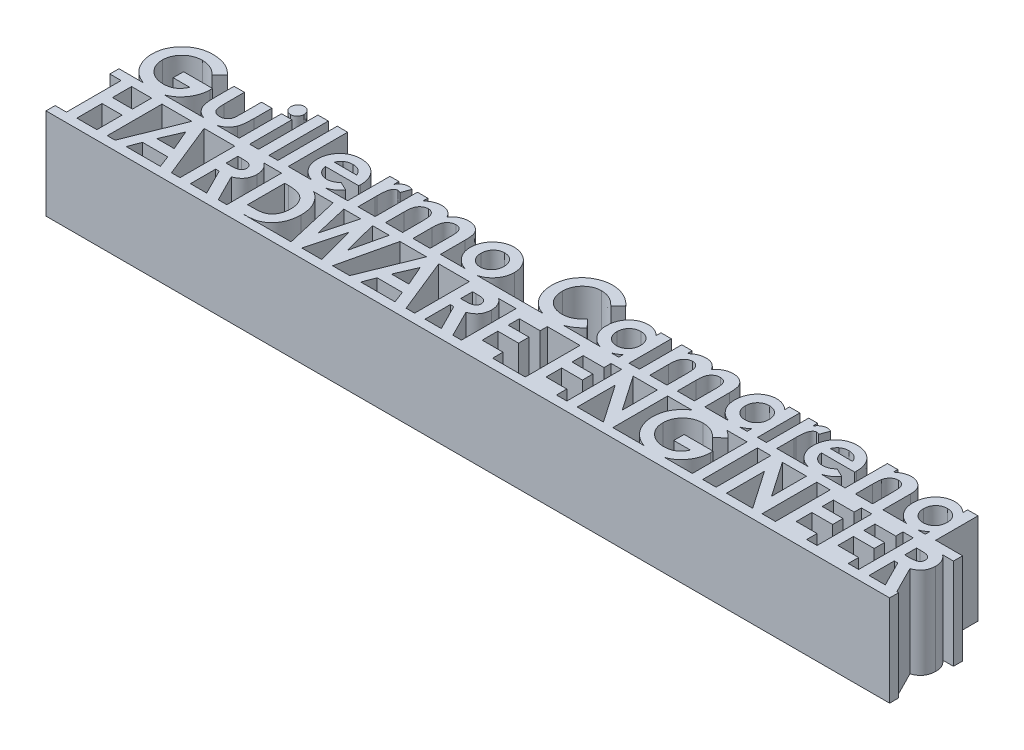
SolidWorks part; units mm, degrees
ref_plane "Front Plane" through (0, 0, 0) normal (0, 0, 1) x (1, 0, 0)
ref_plane "Top Plane" through (0, 0, 0) normal (0, 1, 0) x (1, 0, 0)
ref_plane "Right Plane" through (0, 0, 0) normal (1, 0, 0) x (0, 0, -1)
sketch "Sketch2" plane through (0, 0, 0) normal (0, 1, 0) x (1, 0, 0)
  text T0 "Guillermo Camarena" font "Century Gothic" height in points 48
extrude "Boss-Extrude1" add sketch "Sketch2" along normal blind 20
sketch "Sketch3" plane through (0, 0, 0) normal (0, 1, 0) x (1, 0, 0)
  line L1 (0, 0) -> (185, 0)
  line L2 (0, 0) -> (0, -2)
  line L3 (0, -2) -> (185, -2)
  line L4 (185, 0) -> (185, -2)
  dimension "D1" = 185
  dimension "D2" = 2
extrude "Boss-Extrude2" add sketch "Sketch3" along normal blind 20
sketch "Sketch4" plane through (0, 0, 0) normal (0, 1, 0) x (1, 0, 0)
  line L0 (0, -2) -> (185, -2) construction
  line L1 (0, -14) -> (185, -14)
  line L2 (0, -14) -> (0, -16)
  line L3 (0, -16) -> (185, -16)
  line L4 (185, -14) -> (185, -16)
  dimension "D1" = 185
  dimension "D2" = 2
  dimension "D3" = 12
extrude "Boss-Extrude3" add sketch "Sketch4" along normal blind 20 separate body
sketch "Sketch6" plane through (0, 0, 0) normal (0, 1, 0) x (1, 0, 0)
  text T0 "HARDWARE ENGINEER" font "Century Gothic" height in points 48
extrude "Boss-Extrude4" add sketch "Sketch6" along normal blind 20
